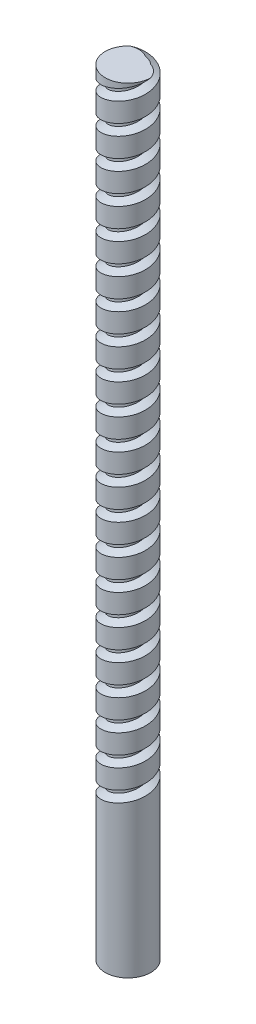
SolidWorks part; units mm, degrees
ref_plane "Front Plane" through (0, 0, 0) normal (0, 0, 1) x (1, 0, 0)
ref_plane "Top Plane" through (0, 0, 0) normal (0, 1, 0) x (1, 0, 0)
ref_plane "Right Plane" through (0, 0, 0) normal (1, 0, 0) x (0, 0, -1)
sketch "Sketch2" plane through (0, 0, 0) normal (0, 1, 0) x (1, 0, 0)
  circle A0 centre (0, 0) radius 3.81
  dimension "D1" = 7.62
extrude "Rod Body" add sketch "Sketch2" along normal blind 132.08
thread "Thread1" pitch 2.1167 method cut profile "Thread Profile2" start angle 0, offset 0, length 106.68, pitch 5.08, diameter 7.62
ref_plane "Plane2" through (-3.81, 132.08, 0) normal (0, 0, 1) x (-1, 0, 0)
sketch "Thread Profile2" plane through (-3.81, 132.08, 0) normal (0, 0, 1) x (-1, 0, 0)
  line L0 (0, 0) -> (0, 2.1167) construction
  line L11 (0, 0) -> (0, 1.8521)
  line L12 (0, 1.8521) -> (-1.1457, 1.1906)
  line L13 (-1.1457, 1.1906) -> (-1.1457, 0.6615)
  line L15 (-1.1457, 0.6615) -> (0, 0)
  line L17 (-1.1457, 0.926) -> (0, 0.926) construction
  point P2 (0, 0)
  dimension "Pitch" = 2.1167
  dimension "Profile_Angle" = 60
  dimension "Profile_Land" = 0.5292
  dimension "Profile_Height" = 1.1457
sketch "Sketch5" plane through (0, 132.08, 0) normal (0, 1, 0) x (1, 0, 0)
  circle A0 centre (0, 0) radius 3.81
  dimension "D1" = 7.62
extrude "Cut-Extrude2" cut sketch "Sketch5" against normal blind 2.54
